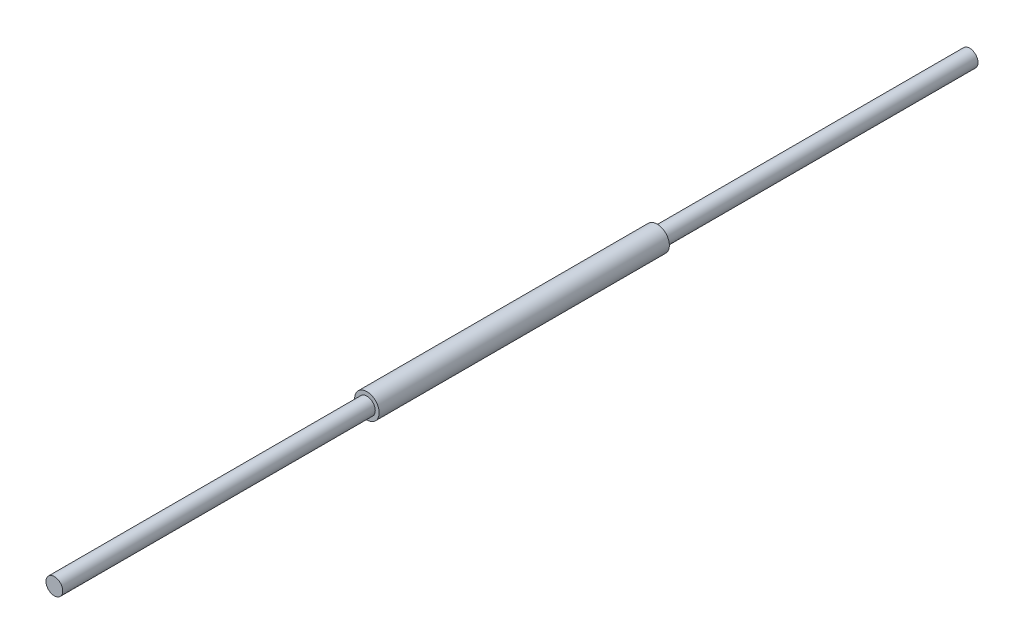
SolidWorks part; units mm, degrees
material "AISI 1020"
ref_plane "Front Plane" through (0, 0, 0) normal (0, 0, 1) x (1, 0, 0)
ref_plane "Top Plane" through (0, 0, 0) normal (0, 1, 0) x (1, 0, 0)
ref_plane "Right Plane" through (0, 0, 0) normal (1, 0, 0) x (0, 0, -1)
sketch "Sketch1" plane through (0, 0, 0) normal (0, 0, 1) x (1, 0, 0)
  circle A0 centre (0, 0) radius 4.7625
  circle A1 centre (0, 0) radius 6.985
  dimension "D1" = 13.97
  dimension "D2" = 9.525
extrude "Boss-Extrude1" add sketch "Sketch1" along normal mid plane 520.7 contours A0 region at (0, 0, 0)
extrude "Boss-Extrude2" add sketch "Sketch1<3>" along normal mid plane 165.1
sketch "Sketch1<3>" plane through (0, 0, 0) normal (0, 0, 1) x (1, 0, 0) same geometry as "Sketch1"
